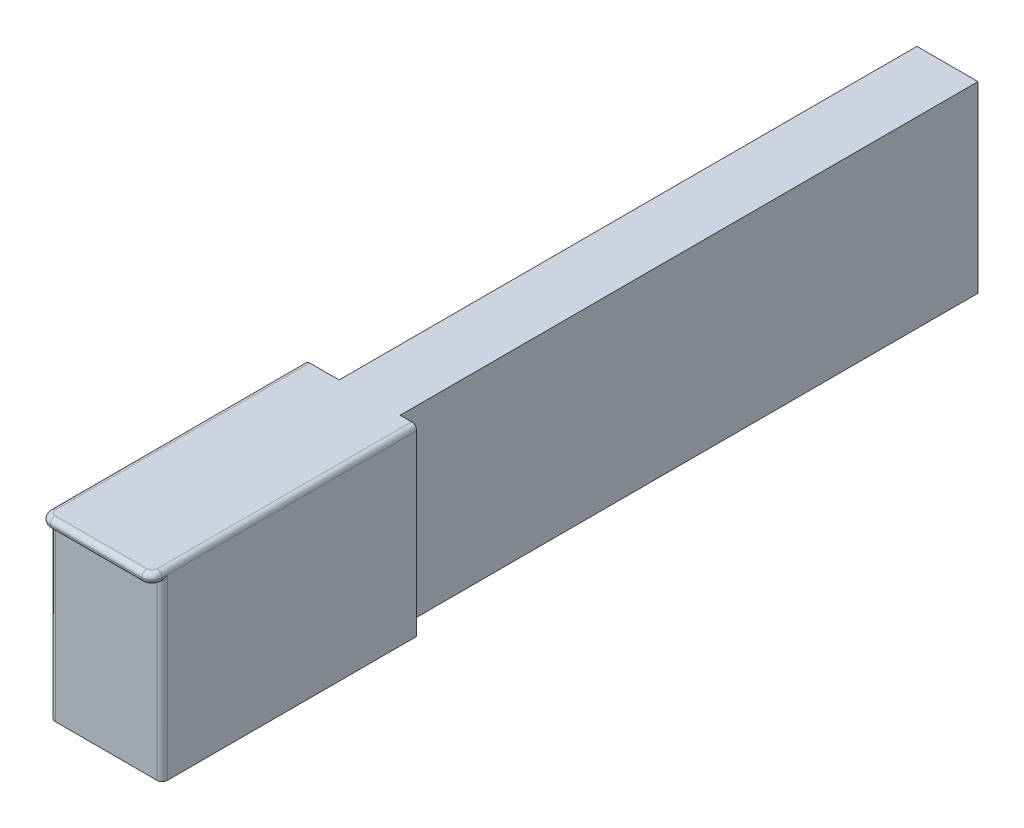
SolidWorks part; units mm, degrees
ref_plane "Front Plane" through (0, 0, 0) normal (0, 0, 1) x (1, 0, 0)
ref_plane "Top Plane" through (0, 0, 0) normal (0, 1, 0) x (1, 0, 0)
ref_plane "Right Plane" through (0, 0, 0) normal (1, 0, 0) x (0, 0, -1)
sketch "Sketch1" plane through (0, 0, 0) normal (0, 1, 0) x (1, 0, 0)
  line L1 (-11, -81.75) -> (11, -81.75)
  line L2 (-11, -81.75) -> (-11, 81.75)
  line L3 (-11, 81.75) -> (11, 81.75)
  line L4 (11, -81.75) -> (11, 81.75)
  line L5 (-11, -81.75) -> (11, 81.75) construction
  line L6 (-11, 81.75) -> (11, -81.75) construction
  point P0 (0, 0)
  dimension "D1" = 163.5
  dimension "D2" = 22
extrude "Boss-Extrude1" add sketch "Sketch1" along normal blind 36 contours L2 L3 L4 L1
fillet "Fillet1" radius 1 2 edges at (-11, 18, 81.75) (11, 18, 81.75)
sketch "Sketch2" plane through (0, 36, 0) normal (0, 1, 0) x (1, 0, 0)
  line L0 (11, -80.75) -> (11, 81.75) construction
  line L1 (-11, 81.75) -> (11, 81.75)
  line L2 (-11, 81.75) -> (-11, -83.75)
  line L3 (-11, -83.75) -> (11, -83.75)
  line L4 (11, 81.75) -> (11, -83.75)
  line L5 (-10, -81.75) -> (10, -81.75) construction
  dimension "D1" = 2
extrude "Boss-Extrude2" add sketch "Sketch2" against normal blind 2
fillet "Fillet2" radius 2 2 edges at (-11, 35, 83.75) (11, 35, 83.75)
fillet "Fillet3" radius 1 10 edges at (-11, 34, 81.25) (-10.4142, 34, 83.1642) (11, 34, 81.25) (10.4142, 34, 83.1642) (11, 36, 0) (10.4142, 36, 83.1642) (0, 36, 83.75) (-10.4142, 36, 83.1642) (-11, 36, 0) (0, 34, 83.75)
sketch "Sketch3" plane through (0, 36, 0) normal (0, 1, 0) x (1, 0, 0)
  line L1 (7.5, -31.75) -> (11, -31.75)
  line L2 (7.5, -31.75) -> (7.5, 81.75)
  line L3 (7.5, 81.75) -> (11, 81.75)
  line L4 (11, -31.75) -> (11, 81.75)
  line L5 (7.5, -31.75) -> (11, 81.75) construction
  line L6 (7.5, 81.75) -> (11, -31.75) construction
  line L7 (-10, -81.75) -> (10, -81.75) construction
  line L8 (-11, 81.75) -> (11, 81.75) construction
  line L9 (11, 81.75) -> (11, -80.75) construction
  dimension "D1" = 3.5
  dimension "D2" = 50
extrude "Cut-Extrude2" [suppressed] cut sketch "Sketch3" against normal through all
sketch "Sketch5" plane through (-11, 0, 0) normal (-1, 0, 0) x (0, 0, 1)
  line L0 (81.75, 34) -> (81.75, 0) construction
  line L1 (80.75, 0) -> (-81.75, 0) construction
  line L2 (-81.75, 36) -> (81.75, 36) construction
  line L3 (-81.75, 35) -> (-81.75, 0) construction
  line L8 (31.75, 36) -> (-81.75, 36)
  line L9 (31.75, 0) -> (31.75, 36)
  line L10 (-81.75, 0) -> (31.75, 0)
  line L11 (-81.75, 36) -> (-81.75, 0)
  dimension "D1" = 50
extrude "Cut-Extrude4" [suppressed] cut sketch "Sketch5" against normal blind 3.5
sketch "Sketch4" [suppressed] plane through (7.5, 0, 0) normal (1, 0, 0) x (0, 0, -1)
  line L4 (81.75, 36) -> (-31.75, 36)
  line L5 (-31.75, 36) -> (-31.75, 0)
  line L6 (-31.75, 0) -> (81.75, 0)
  line L7 (81.75, 0) -> (81.75, 36)
  line L8 (81.75, 36) -> (-31.75, 36)
  line L9 (-31.75, 36) -> (-31.75, 0)
  line L10 (-31.75, 0) -> (81.75, 0)
  line L11 (81.75, 0) -> (81.75, 36)
  dimension "D1" = 0
extrude "Cut-Extrude3" [suppressed] cut sketch "Sketch4" against normal blind 3.25
sketch "Sketch6" [suppressed] plane through (-7.5, 0, 0) normal (-1, 0, 0) x (0, 0, 1)
  line L4 (-81.75, 36) -> (-81.75, 0)
  line L5 (-81.75, 0) -> (31.75, 0)
  line L6 (31.75, 0) -> (31.75, 36)
  line L7 (31.75, 36) -> (-81.75, 36)
  line L8 (-81.75, 36) -> (-81.75, 0)
  line L9 (-81.75, 0) -> (31.75, 0)
  line L10 (31.75, 0) -> (31.75, 36)
  line L11 (31.75, 36) -> (-81.75, 36)
  dimension "D1" = 0
extrude "Cut-Extrude5" [suppressed] cut sketch "Sketch6" against normal blind 3.25
sketch "White" plane through (0, 0, 0) normal (0, 1, 0) x (1, 0, 0)
  line L0 (12.5, -81.75) -> (34.5, -81.75)
  line L1 (-11, -81.75) -> (11, -81.75)
  line L2 (-11, -81.75) -> (-11, 81.75)
  line L3 (-11, 81.75) -> (11, 81.75)
  line L4 (11, -81.75) -> (11, 81.75)
  line L5 (12.5, -81.75) -> (12.5, 81.75)
  line L6 (12.5, 81.75) -> (34.5, 81.75)
  line L7 (34.5, -81.75) -> (34.5, 81.75)
  line L8 (36, -81.75) -> (58, -81.75)
  line L9 (36, -81.75) -> (36, 81.75)
  line L10 (36, 81.75) -> (58, 81.75)
  line L11 (58, -81.75) -> (58, 81.75)
  line L12 (59.5, -81.75) -> (81.5, -81.75)
  line L13 (59.5, -81.75) -> (59.5, 81.75)
  line L14 (59.5, 81.75) -> (81.5, 81.75)
  line L15 (81.5, -81.75) -> (81.5, 81.75)
  line L16 (83, -81.75) -> (105, -81.75)
  line L17 (83, -81.75) -> (83, 81.75)
  line L18 (83, 81.75) -> (105, 81.75)
  line L19 (105, -81.75) -> (105, 81.75)
  line L20 (106.5, -81.75) -> (128.5, -81.75)
  line L21 (106.5, -81.75) -> (106.5, 81.75)
  line L22 (106.5, 81.75) -> (128.5, 81.75)
  line L23 (128.5, -81.75) -> (128.5, 81.75)
  line L24 (130, -81.75) -> (152, -81.75)
  line L25 (130, -81.75) -> (130, 81.75)
  line L26 (130, 81.75) -> (152, 81.75)
  line L27 (152, -81.75) -> (152, 81.75)
  dimension "D1" = 7
sketch "Black" plane through (0, 0, 0) normal (0, 1, 0) x (1, 0, 0)
  line L0 (-11, 81.75) -> (11, 81.75) construction
  line L1 (16, -31.75) -> (4, -31.75)
  line L2 (16, -31.75) -> (16, 81.75)
  line L3 (16, 81.75) -> (4, 81.75)
  line L4 (4, -31.75) -> (4, 81.75)
  line L6 (31, -31.75) -> (43, -31.75)
  line L7 (31, -31.75) -> (31, 81.75)
  line L8 (31, 81.75) -> (43, 81.75)
  line L9 (43, -31.75) -> (43, 81.75)
  line L10 (12.5, -81.75) -> (34.5, -81.75) construction
  line L11 (16, -31.75) -> (31, -31.75) construction
  line L12 (36, 81.75) -> (58, 81.75) construction
  line L13 (106.5, 81.75) -> (128.5, 81.75) construction
  line L14 (111.75, 81.75) -> (99.75, 81.75)
  line L15 (111.75, 81.75) -> (111.75, -31.75)
  line L16 (111.75, -31.75) -> (99.75, -31.75)
  line L17 (99.75, 81.75) -> (99.75, -31.75)
  line L18 (83, 81.75) -> (105, 81.75) construction
  line L19 (126.75, 81.75) -> (138.75, 81.75)
  line L20 (126.75, 81.75) -> (126.75, -31.75)
  line L21 (126.75, -31.75) -> (138.75, -31.75)
  line L22 (138.75, 81.75) -> (138.75, -31.75)
  line L23 (84.75, 81.75) -> (72.75, 81.75)
  line L24 (84.75, 81.75) -> (84.75, -31.75)
  line L25 (84.75, -31.75) -> (72.75, -31.75)
  line L26 (72.75, 81.75) -> (72.75, -31.75)
  line L27 (105, -81.75) -> (106.5, -81.75) construction
  point P14 (23.5, -81.75)
  point P15 (23.5, -31.75)
  point P36 (105.75, -81.75)
  point P37 (105.75, -31.75)
  dimension "D1" = 50
  dimension "D2" = 12
  dimension "D3" = 12
  dimension "D4" = 15
  dimension "D5" = 15
  dimension "D6" = 15
sketch "Sketch11" plane through (0, 36, 0) normal (0, 1, 0) x (1, 0, 0)
  line L1 (11, 81.75) -> (2.5, 81.75)
  line L2 (11, 81.75) -> (11, -31.75)
  line L3 (11, -31.75) -> (2.5, -31.75)
  line L4 (2.5, 81.75) -> (2.5, -31.75)
  line L5 (16, -31.75) -> (4, -31.75) construction
  dimension "D1" = 8.5
extrude "C" [suppressed] cut sketch "Sketch11" against normal through all
sketch "Sketch12" plane through (0, 36, 0) normal (0, 1, 0) x (1, 0, 0)
  line L0 (31, -31.75) -> (43, -31.75) construction
  line L1 (-11, 81.75) -> (-6, 81.75)
  line L2 (-11, 81.75) -> (-11, -31.75)
  line L3 (-11, -31.75) -> (-6, -31.75)
  line L4 (-6, 81.75) -> (-6, -31.75)
  line L5 (11, 81.75) -> (6, 81.75)
  line L6 (11, 81.75) -> (11, -31.75)
  line L7 (11, -31.75) -> (6, -31.75)
  line L8 (6, 81.75) -> (6, -31.75)
  dimension "D1" = 5
  dimension "D2" = 5
extrude "D" [suppressed] cut sketch "Sketch12" against normal through all
sketch "Sketch13" plane through (0, 36, 0) normal (0, 1, 0) x (1, 0, 0)
  line L1 (-11, 81.75) -> (-2.5, 81.75)
  line L2 (-11, 81.75) -> (-11, -31.75)
  line L3 (-11, -31.75) -> (-2.5, -31.75)
  line L4 (-2.5, 81.75) -> (-2.5, -31.75)
  line L5 (16, -31.75) -> (4, -31.75) construction
  dimension "D1" = 8.5
extrude "E" [suppressed] cut sketch "Sketch13" against normal through all
sketch "Sketch14" plane through (0, 36, 0) normal (0, 1, 0) x (1, 0, 0)
  line L0 (16, -31.75) -> (4, -31.75) construction
  line L1 (11, 81.75) -> (0.75, 81.75)
  line L2 (11, 81.75) -> (11, -31.75)
  line L3 (11, -31.75) -> (0.75, -31.75)
  line L4 (0.75, 81.75) -> (0.75, -31.75)
  dimension "D1" = 10.25
extrude "F" [suppressed] cut sketch "Sketch14" against normal through all
sketch "Sketch15" plane through (0, 36, 0) normal (0, 1, 0) x (1, 0, 0)
  line L1 (-11, 81.75) -> (-7.75, 81.75)
  line L2 (-11, 81.75) -> (-11, -31.75)
  line L3 (-11, -31.75) -> (-7.75, -31.75)
  line L4 (-7.75, 81.75) -> (-7.75, -31.75)
  line L5 (11, 81.75) -> (4.25, 81.75)
  line L6 (11, 81.75) -> (11, -31.75)
  line L7 (11, -31.75) -> (4.25, -31.75)
  line L8 (4.25, 81.75) -> (4.25, -31.75)
  line L9 (16, -31.75) -> (4, -31.75) construction
  dimension "D1" = 3.25
  dimension "D2" = 6.75
extrude "G" [suppressed] cut sketch "Sketch15" against normal through all
sketch "Sketch16" plane through (0, 36, 0) normal (0, 1, 0) x (1, 0, 0)
  line L0 (16, -31.75) -> (4, -31.75) construction
  line L1 (-11, 81.75) -> (-4.25, 81.75)
  line L2 (-11, 81.75) -> (-11, -31.75)
  line L3 (-11, -31.75) -> (-4.25, -31.75)
  line L4 (-4.25, 81.75) -> (-4.25, -31.75)
  line L5 (11, 81.75) -> (7.75, 81.75)
  line L6 (11, 81.75) -> (11, -31.75)
  line L7 (11, -31.75) -> (7.75, -31.75)
  line L8 (7.75, 81.75) -> (7.75, -31.75)
  dimension "D1" = 6.75
  dimension "D2" = 3.25
extrude "A" cut sketch "Sketch16" against normal through all
sketch "Sketch17" plane through (0, 36, 0) normal (0, 1, 0) x (1, 0, 0)
  line L0 (16, -31.75) -> (4, -31.75) construction
  line L1 (-11, 81.75) -> (-0.75, 81.75)
  line L2 (-11, 81.75) -> (-11, -31.75)
  line L3 (-11, -31.75) -> (-0.75, -31.75)
  line L4 (-0.75, 81.75) -> (-0.75, -31.75)
  dimension "D1" = 10.25
extrude "B" [suppressed] cut sketch "Sketch17" against normal through all
